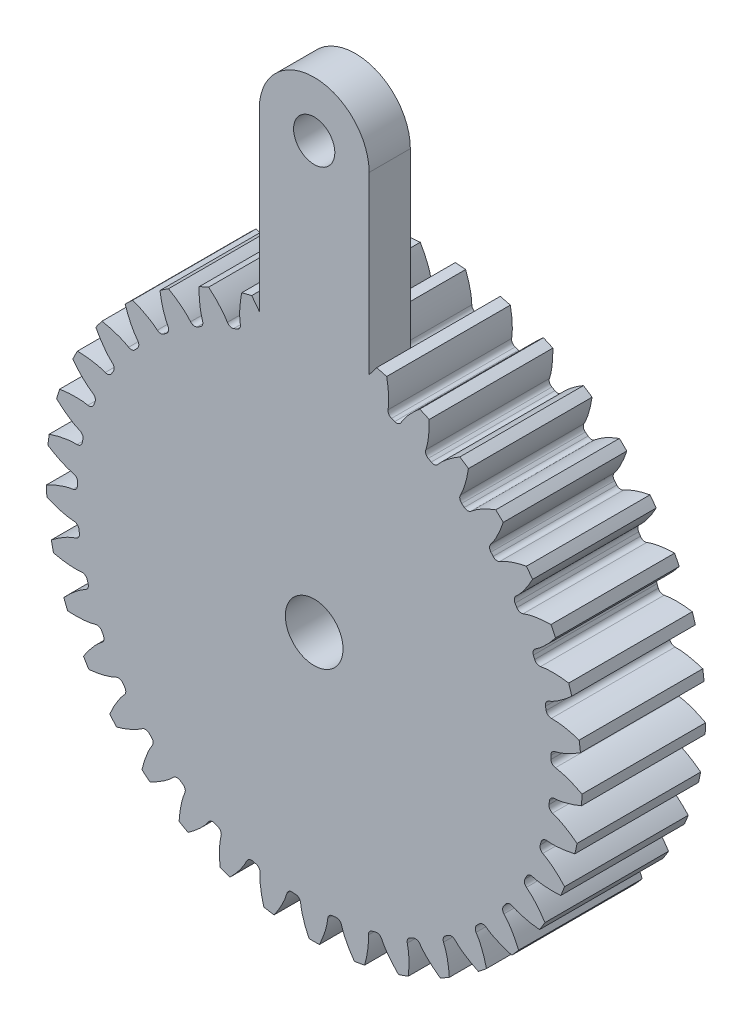
SolidWorks part; units mm, degrees
material "Vero PureWhite"
ref_plane "前视基准面" through (0, 0, 0) normal (0, 0, 1) x (1, 0, 0)
ref_plane "上视基准面" through (0, 0, 0) normal (0, 1, 0) x (1, 0, 0)
ref_plane "右视基准面" through (0, 0, 0) normal (1, 0, 0) x (0, 0, -1)
other "Configuration Table"
ref_axis "Axis1" through (0, 0, -88.99) along (0, 0, 1)
sketch "草图1" plane through (0, 0, 0) normal (0, 0, 1) x (1, 0, 0)
  circle A0 centre (0, 0) radius 19.5
extrude "LaShenA" add sketch "草图1" along normal blind 9
sketch "SketchA" plane through (0, 0, 9) normal (0, 0, 1) x (1, 0, 0)
  line L0 (0, 0) -> (0, 19.5) construction
  arc A0 (0.1249, 17.2495) -> (-0.1249, 17.2495) centre (0, 0) ccw
  arc A1 (1.6316, 20.0089) -> (-1.6316, 20.0089) centre (0, 0) ccw
  arc A2 (-0.1249, 17.2495) -> (-0.5007, 17.5572) centre (-0.1277, 17.6295) cw
  arc A3 (0.5007, 17.5572) -> (0.1249, 17.2495) centre (0.1277, 17.6295) cw
  circle A4 centre (0, 0) radius 17.3843 construction
  circle A5 centre (0, 0) radius 19.5 construction
  circle A6 centre (0, 0) radius 17.25 construction
  circle A7 centre (0, 0) radius 18.5 construction
  spline S0 degree 3 poles (0.5007, 17.5572) (0.5047, 17.5775) (0.5148, 17.6293) (0.5294, 17.6986) (0.5455, 17.7663) (0.5598, 17.8228) (0.576, 17.8829) (0.5942, 17.9466) (0.6146, 18.0138) (0.6372, 18.0846) (0.6621, 18.1588) (0.6895, 18.2365) (0.7195, 18.3174) (0.7521, 18.4017) (0.7876, 18.4892) (0.8259, 18.5798) (0.8672, 18.6735) (0.9116, 18.7702) (0.9592, 18.8699) (1.0101, 18.9724) (1.0644, 19.0777) (1.1222, 19.1857) (1.1835, 19.2963) (1.2486, 19.4095) (1.3174, 19.5251) (1.39, 19.6431) (1.4936, 19.8057) (1.5752, 19.9275) (1.6316, 20.0089) knots 0.105238 0.105238 0.105238 0.105238 0.125626 0.157343 0.175185 0.194349 0.214835 0.236643 0.259774 0.284226 0.31 0.337096 0.365514 0.395255 0.426317 0.458701 0.492408 0.527436 0.563786 0.601458 0.640453 0.680769 0.722408 0.765368 0.80965 0.855255 0.902181 1 1 1 1
  spline S1 degree 3 poles (-0.5007, 17.5572) (-0.5047, 17.5775) (-0.5148, 17.6293) (-0.5294, 17.6986) (-0.5455, 17.7663) (-0.5598, 17.8228) (-0.576, 17.8829) (-0.5942, 17.9466) (-0.6146, 18.0138) (-0.6372, 18.0846) (-0.6621, 18.1588) (-0.6895, 18.2365) (-0.7195, 18.3174) (-0.7521, 18.4017) (-0.7876, 18.4892) (-0.8259, 18.5798) (-0.8672, 18.6735) (-0.9116, 18.7702) (-0.9592, 18.8699) (-1.0101, 18.9724) (-1.0644, 19.0777) (-1.1222, 19.1857) (-1.1835, 19.2963) (-1.2486, 19.4095) (-1.3174, 19.5251) (-1.39, 19.6431) (-1.4936, 19.8057) (-1.5752, 19.9275) (-1.6316, 20.0089) knots 0.105238 0.105238 0.105238 0.105238 0.125626 0.157343 0.175185 0.194349 0.214835 0.236643 0.259774 0.284226 0.31 0.337096 0.365514 0.395255 0.426317 0.458701 0.492408 0.527436 0.563786 0.601458 0.640453 0.680769 0.722408 0.765368 0.80965 0.855255 0.902181 1 1 1 1
  dimension "D1" = 0.38
  dimension "Db" = 34.7686
  dimension "Da" = 39
  dimension "Df" = 34.5
  dimension "Dn" = 37
extrude "Cut-ExtrudeA" cut sketch "SketchA" against normal blind 10
pattern_circular "www.KYTool.cn" count 37 over 360 about axis through (0, 0, -88.99) along (0, 0, 1) of "Cut-ExtrudeA"
sketch "草图3" plane through (0, 0, 9) normal (0, 0, 1) x (1, 0, 0)
  line L0 (0, 0) -> (0, 31) construction
  line L1 (-4, 0) -> (-4, 31)
  line L2 (4, 0) -> (4, 31)
  arc A0 (-4, 0) -> (4, 0) centre (0, 0) ccw
  arc A1 (4, 31) -> (-4, 31) centre (0, 31) ccw
  point P3 (0, 15.5)
  dimension "D2" = 4
  dimension "D1" = 31
extrude "凸台-拉伸2" add sketch "草图3" against normal blind 3
sketch "草图4" plane through (0, 0, 6) normal (0, 0, -1) x (-1, 0, 0)
  circle A0 centre (0, 31) radius 1.5
  dimension "D1" = 3
extrude "切除-拉伸2" cut sketch "草图4" against normal through all
sketch "草图5" plane through (0, 0, 0) normal (0, 0, -1) x (-1, 0, 0)
  circle A0 centre (0, 0) radius 2.1
  dimension "D1" = 4.2
extrude "切除-拉伸3" cut sketch "草图5" against normal through all
